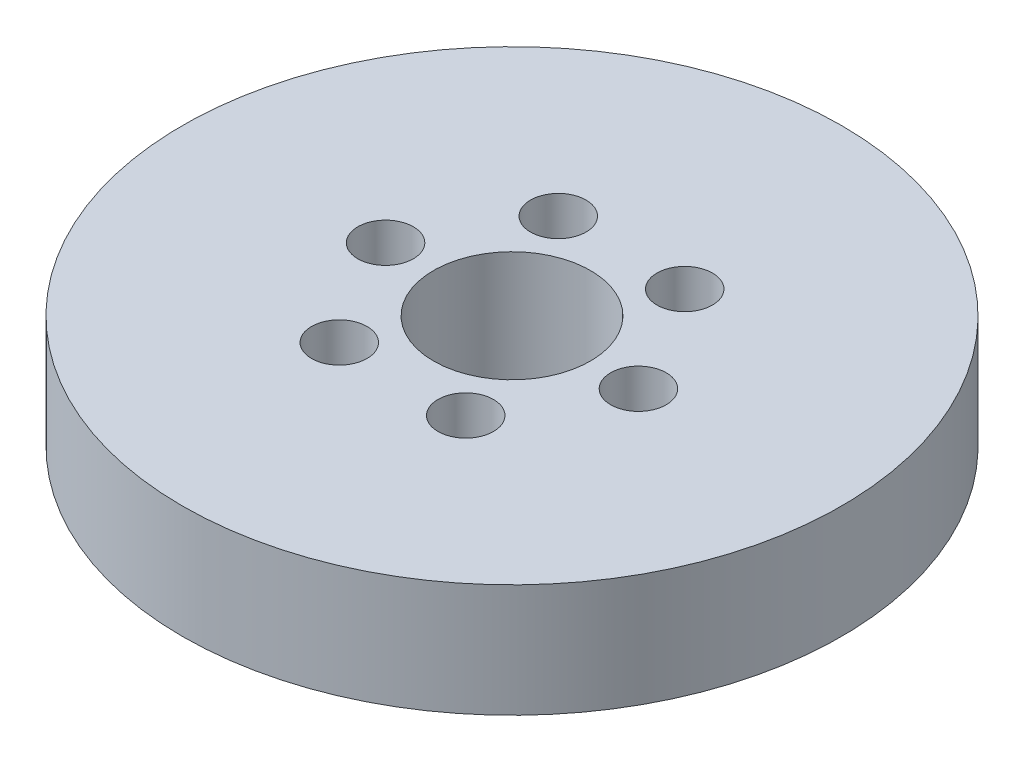
SolidWorks part; units mm, degrees
ref_plane "Front Plane" through (0, 0, 0) normal (0, 0, 1) x (1, 0, 0)
ref_plane "Top Plane" through (0, 0, 0) normal (0, 1, 0) x (1, 0, 0)
ref_plane "Right Plane" through (0, 0, 0) normal (1, 0, 0) x (0, 0, -1)
sketch "Sketch1" plane through (0, 0, 0) normal (0, 1, 0) x (1, 0, 0)
  circle A0 centre (0, 0) radius 52.5
  dimension "FLANGE_OD" = 105
extrude "Boss-Extrude1" add sketch "Sketch1" along normal blind 18
sketch "Sketch2" plane through (0, 0, 0) normal (0, 1, 0) x (1, 0, 0)
  circle A0 centre (0, 0) radius 12.5
  dimension "BORE_D" = 25
extrude "Cut-Extrude1" cut sketch "Sketch2" along normal through all
sketch "Sketch3" plane through (0, 18, 0) normal (0, 1, 0) x (1, 0, 0)
  circle A0 centre (0, 0) radius 20.1409 construction
  circle A1 centre (-20.1409, 0) radius 4.424
  dimension "BOLT_D" = 8.8481
  dimension "BOLT_PCD" = 40.2818
extrude "Cut-Extrude2" cut sketch "Sketch3" against normal blind 14.6668
pattern_circular "CirPattern1" count 6 over 360 about axis through (0, 0, 0) along (0, 1, 0) of "Cut-Extrude2"
